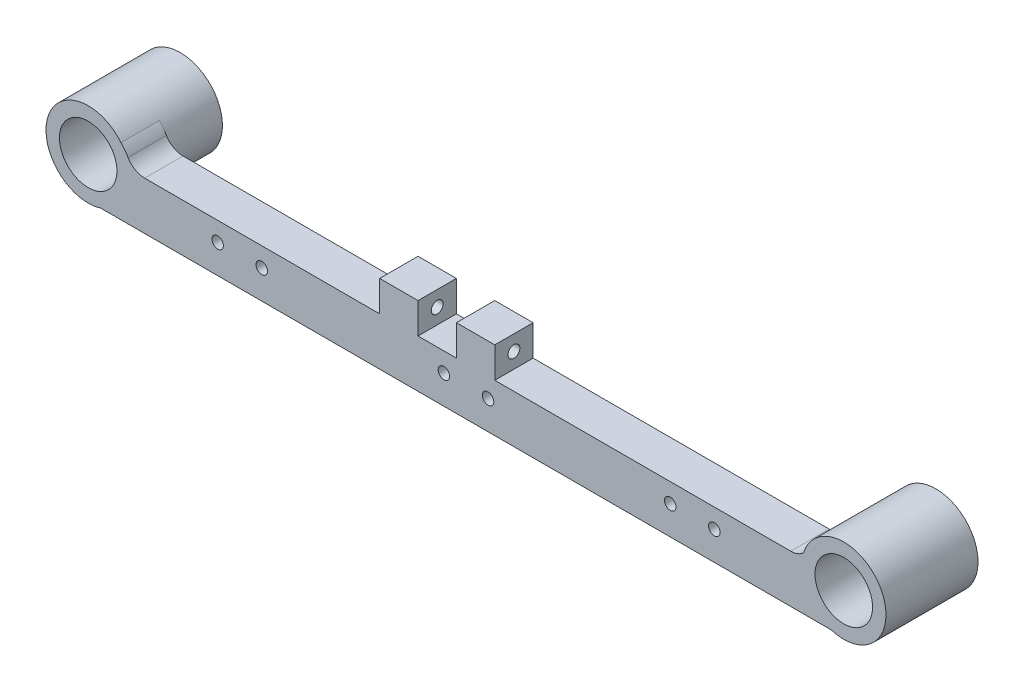
SolidWorks part; units mm, degrees
ref_plane "Front Plane" through (0, 0, 0) normal (0, 0, 1) x (1, 0, 0)
ref_plane "Top Plane" through (0, 0, 0) normal (0, 1, 0) x (1, 0, 0)
ref_plane "Right Plane" through (0, 0, 0) normal (1, 0, 0) x (0, 0, -1)
sketch "Sketch2" plane through (0, 0, 0) normal (0, 0, 1) x (1, 0, 0)
  line L0 (-98.5, 4.8316) -> (98.5, 4.8316) construction
  line L5 (-22.5, 6.8316) -> (-22.5, 14.8316)
  line L6 (-22.5, 14.8316) -> (-12.5, 14.8316)
  line L7 (-98.5, -5.6684) -> (98.5, -5.6684)
  line L10 (-87.0218, 6.8316) -> (-22.5, 6.8316)
  line L13 (7.5, 14.8316) -> (7.5, 6.8316)
  line L14 (7.5, 6.8316) -> (88.1922, 6.8316)
  line L15 (-12.5, 14.8316) -> (-12.5, 6.8316)
  line L16 (-12.5, 6.8316) -> (-2.5, 6.8316)
  line L17 (-2.5, 6.8316) -> (-2.5, 14.8316)
  line L18 (-2.5, 14.8316) -> (7.5, 14.8316)
  circle A0 centre (-98.5, 4.8316) radius 7.5
  circle A1 centre (98.5, 4.8316) radius 7.5
  arc A2 (-98.5, 15.3316) -> (-98.5, -5.6684) centre (-98.5, 4.8316) ccw
  arc A3 (98.5, -5.6684) -> (98.5, 15.3316) centre (98.5, 4.8316) ccw
  arc A4 (-98.5, 15.3316) -> (-87.0218, 6.8316) centre (-98.5, 3.3316) cw
  arc A5 (98.5, 15.3316) -> (88.1922, 6.8316) centre (98.5, 4.8316) ccw
  point P0 (0, 0)
  point P10 (0, 4.8316)
  dimension "D1" = 15
  dimension "D3" = 3
  dimension "D9" = 12
  dimension "D2" = 197
  dimension "D4" = 12.5
  dimension "D5" = 22.5
  dimension "D6" = 30
  dimension "D7" = 8
  dimension "D8" = 10
extrude "Boss-Extrude1" add sketch "Sketch2" along normal blind 10
fillet "Fillet1" radius 5 1 edges at (88.1922, 6.8316, 5)
fillet "Fillet2" radius 5 1 edges at (-87.0218, 6.8316, 5)
sketch "Sketch3" plane through (0, 0, 10) normal (0, 0, 1) x (1, 0, 0)
  circle A0 centre (-98.5, 4.8316) radius 7.5
  circle A1 centre (-98.5, 4.8316) radius 11
  dimension "D1" = 15
  dimension "D2" = 22
extrude "Boss-Extrude2" add sketch "Sketch3" against normal blind 24
mirror "Mirror1" about plane through (0, 0, 0) normal (1, 0, 0) of "Boss-Extrude2"
sketch "Sketch4" plane through (-22.5, 0, 0) normal (-1, 0, 0) x (0, 0, 1)
  line L0 (10, 14.8316) -> (0, 14.8316) construction
  line L1 (0, 14.8316) -> (0, 6.8316) construction
  circle A0 centre (5, 10.8316) radius 1.55
  point P4 (5, 14.8316)
  point P7 (0, 10.8316)
  dimension "D1" = 3.1
extrude "Cut-Extrude1" cut sketch "Sketch4" against normal up to surface (30 mm away) up to face at (7.5, 10.8316, 5)
sketch "Sketch5" plane through (0, 0, 10) normal (0, 0, 1) x (1, 0, 0)
  line L0 (-95.2213, -5.6684) -> (95.2213, -5.6684) construction
  line L2 (-5.75, 1.83) -> (5.75, 1.83) construction
  circle A0 centre (-64.75, 1.83) radius 1.5
  circle A1 centre (-53.25, 1.83) radius 1.5
  circle A2 centre (-5.75, 1.83) radius 1.5
  circle A3 centre (5.75, 1.83) radius 1.5
  circle A4 centre (53.25, 1.83) radius 1.5
  circle A5 centre (64.75, 1.83) radius 1.5
  point P12 (0, -5.6684)
  point P15 (0, 1.83)
  dimension "D1" = 3
  dimension "D2" = 11.5
  dimension "D3" = 11.5
  dimension "D4" = 11.5
  dimension "D5" = 7.4984
  dimension "D6" = 59
  dimension "D7" = 59
extrude "Cut-Extrude2" cut sketch "Sketch5" against normal through all
